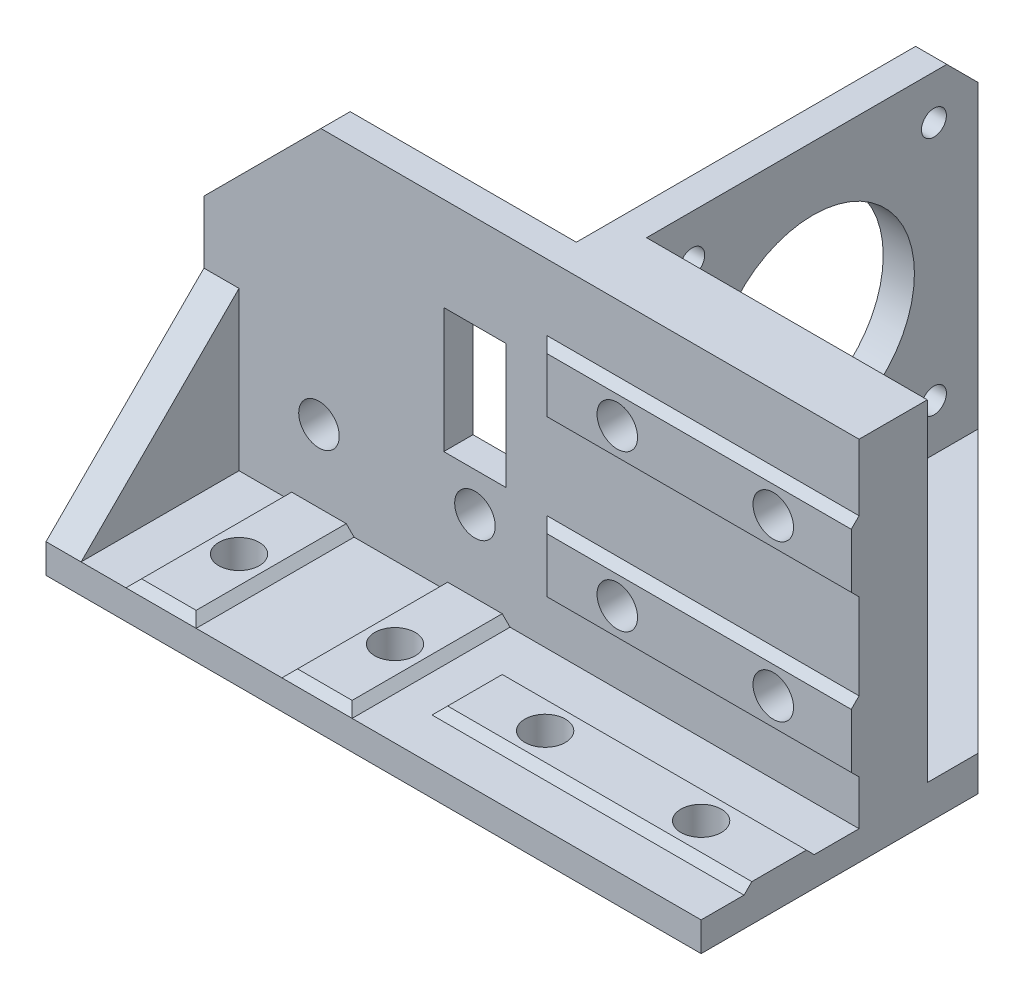
SolidWorks part; units mm, degrees
ref_plane "Front Plane" through (0, 0, 0) normal (0, 0, 1) x (1, 0, 0)
ref_plane "Top Plane" through (0, 0, 0) normal (0, 1, 0) x (1, 0, 0)
ref_plane "Right Plane" through (0, 0, 0) normal (1, 0, 0) x (0, 0, -1)
sketch "Sketch1" plane through (0, 0, 0) normal (0, 0, 1) x (1, 0, 0)
  line L1 (0, 0) -> (84, 0)
  line L2 (15, 47) -> (84, 47)
  line L4 (0, 0) -> (0, 32)
  line L6 (15, 47) -> (0, 32)
  line L7 (84, 0) -> (84, 47)
  point P0 (0, 0)
  point P3 (84.7338, 47)
  dimension "D1" = 32
  dimension "D2" = 84
  dimension "D3" = 69
  dimension "D4" = 135
extrude "Boss-Extrude1" add sketch "Sketch1" along normal blind 8.75
sketch "Sketch2" plane through (0, 0, 0) normal (0, 0, -1) x (-1, 0, 0)
  line L0 (0, 0) -> (-44, 0)
  line L1 (0, 0) -> (-84, 0) construction
  line L2 (-44, 0) -> (-44, 47)
  line L3 (-84, 47) -> (-15, 47) construction
  line L4 (-44, 47) -> (-15, 47)
  line L5 (-15, 47) -> (0, 32)
  line L6 (0, 32) -> (0, 0)
  dimension "D1" = 44
extrude "Cut-Extrude1" cut sketch "Sketch2" against normal blind 5
sketch "Sketch3" plane through (44, 0, 0) normal (-1, 0, 0) x (0, 0, 1)
  line L0 (5, 47) -> (5, 0) construction
  line L1 (0, 47) -> (-38.5, 47)
  line L2 (0, 47) -> (0, 0)
  line L3 (0, 0) -> (-42.5, 0)
  line L4 (-42.5, 43) -> (-42.5, 0)
  line L5 (-38.5, 47) -> (-42.5, 43)
  point P3 (-42.5, 47)
  point P7 (0, 4.3962)
  dimension "D1" = 47.5
extrude "Boss-Extrude2" add sketch "Sketch3" against normal blind 4
sketch "Sketch4" plane through (0, 0, 0) normal (0, -1, 0) x (1, 0, 0)
  line L0 (48, 0) -> (84, 0)
  line L1 (84, 0) -> (84, -6.5)
  line L2 (84, -6.5) -> (48, -42.5)
  line L4 (48, -42.5) -> (48, 0)
  point P4 (62.1757, -28.3243)
  point P9 (48.7974, -41.7026)
  dimension "D1" = 6.5
extrude "Boss-Extrude3" add sketch "Sketch4" against normal blind 4.5
sketch "Sketch5" plane through (0, 0, 0) normal (0, -1, 0) x (1, 0, 0)
  line L0 (44, 5) -> (0, 5) construction
  line L1 (0, 8.75) -> (84, 8.75)
  line L2 (0, 8.75) -> (0, 29)
  line L3 (0, 29) -> (84, 29)
  line L4 (84, 8.75) -> (84, 29)
  point P5 (0, 0)
  dimension "D1" = 24
extrude "Boss-Extrude4" add sketch "Sketch5" against normal blind 3.75
sketch "Sketch6" plane through (0, 0, 0) normal (-1, 0, 0) x (0, 0, 1)
  line L0 (8.75, 3.75) -> (29, 3.75)
  line L1 (29, 3.75) -> (8.75, 24)
  line L2 (8.75, 32) -> (8.75, 3.75) construction
  line L3 (8.75, 24) -> (8.75, 3.75)
  dimension "D1" = 45
extrude "Boss-Extrude5" add sketch "Sketch6" against normal blind 4.5
sketch "Sketch7" plane through (0, 3.75, 0) normal (0, 1, 0) x (1, 0, 0)
  line L0 (84, -8.75) -> (84, -29) construction
  line L1 (84, -23.5) -> (44, -23.5)
  line L2 (84, -23.5) -> (84, -14.5)
  line L3 (84, -14.5) -> (44, -14.5)
  line L4 (44, -23.5) -> (44, -14.5)
  line L5 (84, -29) -> (4.5, -29) construction
  line L6 (10.25, -29) -> (19.25, -29)
  line L7 (10.25, -29) -> (10.25, -8.75)
  line L8 (10.25, -8.75) -> (19.25, -8.75)
  line L9 (19.25, -29) -> (19.25, -8.75)
  line L10 (4.5, -8.75) -> (84, -8.75) construction
  line L11 (4.5, -29) -> (4.5, -8.75) construction
  line L12 (30.25, -8.75) -> (39.25, -8.75)
  line L13 (30.25, -8.75) -> (30.25, -29)
  line L14 (30.25, -29) -> (39.25, -29)
  line L15 (39.25, -8.75) -> (39.25, -29)
  dimension "D1" = 9
  dimension "D2" = 5.75
  dimension "D3" = 40
  dimension "D4" = 9
  dimension "D5" = 5.5
  dimension "D6" = 11
  dimension "D7" = 9
extrude "Boss-Extrude6" add sketch "Sketch7" along normal blind 1
sketch "Sketch8" plane through (0, 0, 8.75) normal (0, 0, 1) x (1, 0, 0)
  line L0 (84, 3.75) -> (84, 47) construction
  line L1 (84, 9.5) -> (44, 9.5)
  line L2 (84, 9.5) -> (84, 18.5)
  line L3 (84, 18.5) -> (44, 18.5)
  line L4 (44, 9.5) -> (44, 18.5)
  line L5 (39.25, 3.75) -> (84, 3.75) construction
  line L6 (84, 38.5) -> (44, 38.5)
  line L7 (84, 38.5) -> (84, 29.5)
  line L8 (84, 29.5) -> (44, 29.5)
  line L9 (44, 38.5) -> (44, 29.5)
  point P10 (0, 0)
  dimension "D1" = 40
  dimension "D2" = 9
  dimension "D3" = 11
  dimension "D4" = 9
  dimension "D5" = 5.75
extrude "Boss-Extrude7" add sketch "Sketch8" along normal blind 1
chamfer "Chamfer1" distance 1 angle 45 15 edges at (19.25, 4.75, 18.875) (14.75, 4.75, 29) (10.25, 4.75, 18.875) (30.25, 4.75, 18.875) (34.75, 4.75, 29) (39.25, 4.75, 18.875) (64, 4.75, 14.5) (64, 4.75, 23.5) (44, 4.75, 19) (64, 29.5, 9.75) (44, 34, 9.75) (64, 38.5, 9.75) (64, 9.5, 9.75) (64, 18.5, 9.75) (44, 14, 9.75)
sketch "Sketch9" plane through (0, 4.75, 0) normal (0, 1, 0) x (1, 0, 0)
  line L0 (18.25, -28) -> (18.25, -8.75) construction
  line L1 (31.25, -8.75) -> (31.25, -28) construction
  line L2 (84, -15.5) -> (45, -15.5) construction
  line L3 (11.25, -28) -> (18.25, -28) construction
  line L4 (84, -22.5) -> (84, -15.5) construction
  circle A0 centre (14.75, -19) radius 2.6
  circle A1 centre (34.75, -19) radius 2.6
  circle A2 centre (54, -19) radius 2.6
  circle A3 centre (74, -19) radius 2.6
  point P18 (0, 0)
  point P19 (0, 0)
  dimension "D1" = 5.2
  dimension "D2" = 5.2
  dimension "D3" = 5.2
  dimension "D4" = 5.2
  dimension "D5" = 3.5
  dimension "D6" = 3.5
  dimension "D7" = 3.5
  dimension "D8" = 9
  dimension "D9" = 20
  dimension "D10" = 10
extrude "Cut-Extrude2" cut sketch "Sketch9" against normal up to next
sketch "Sketch10" plane through (0, 0, 9.75) normal (0, 0, 1) x (1, 0, 0)
  line L0 (4.5, 3.75) -> (4.5, 24) construction
  line L1 (38.75, 35) -> (30.75, 35)
  line L2 (38.75, 35) -> (38.75, 19)
  line L3 (38.75, 19) -> (30.75, 19)
  line L4 (30.75, 35) -> (30.75, 19)
  line L5 (4.5, 3.75) -> (10.25, 3.75) construction
  line L6 (84, 17.5) -> (45, 17.5) construction
  line L7 (84, 10.5) -> (84, 17.5) construction
  line L8 (84, 37.5) -> (45, 37.5) construction
  line L10 (19.25, 3.75) -> (30.25, 3.75) construction
  circle A0 centre (54, 34) radius 2.6
  circle A1 centre (74, 34) radius 2.6
  circle A2 centre (54, 14) radius 2.6
  circle A3 centre (74, 14) radius 2.6
  circle A4 centre (34.75, 14) radius 2.6
  circle A5 centre (14.75, 14) radius 2.6
  point P28 (0, 0)
  point P29 (0, 0)
  point P30 (0, 0)
  point P31 (0, 0)
  point P32 (0, 0)
  point P33 (0, 0)
  dimension "D3" = 5.2
  dimension "D4" = 10.25
  dimension "D5" = 20
  dimension "D6" = 10.25
  dimension "D7" = 3.5
  dimension "D8" = 10
  dimension "D9" = 20
  dimension "D10" = 3.5
  dimension "D1" = 8
  dimension "D2" = 16
  dimension "D11" = 26.25
  dimension "D12" = 31.25
extrude "Cut-Extrude3" cut sketch "Sketch10" against normal up to next
sketch "Sketch12" plane through (0, 0, 0) normal (0, 0, -1) x (-1, 0, 0)
  circle A0 centre (-54, 34) radius 4.5
  circle A1 centre (-74, 34) radius 4.5
  circle A2 centre (-74, 14) radius 4.5
  circle A3 centre (-54, 14) radius 4.5
  dimension "D1" = 9
extrude "Cut-Extrude4" cut sketch "Sketch12" against normal blind 5
sketch "Sketch13" plane through (48, 0, 0) normal (1, 0, 0) x (0, 0, -1)
  line L0 (0, 47) -> (38.5, 47) construction
  line L1 (0, 4.5) -> (0, 47) construction
  line L2 (42.5, 43) -> (42.5, 4.5) construction
  line L3 (0, 4.5) -> (42.5, 4.5) construction
  circle A0 centre (5.85, 41.35) radius 1.6
  circle A1 centre (36.85, 41.35) radius 1.6
  circle A2 centre (36.85, 10.5) radius 1.6
  circle A3 centre (5.85, 10.5) radius 1.6
  circle A4 centre (21.35, 25.85) radius 13
  point P10 (5.265, 10.5942)
  point P11 (0, 0)
  point P20 (0, 0)
  point P21 (0, 0)
  point P22 (0, 0)
  point P23 (0, 0)
  dimension "D1" = 26
  dimension "D2" = 3.2
  dimension "D3" = 5.65
  dimension "D4" = 5.85
  dimension "D5" = 5.65
  dimension "D6" = 6
  dimension "D7" = 21.15
  dimension "D8" = 21.15
extrude "Cut-Extrude5" cut sketch "Sketch13" against normal up to next
